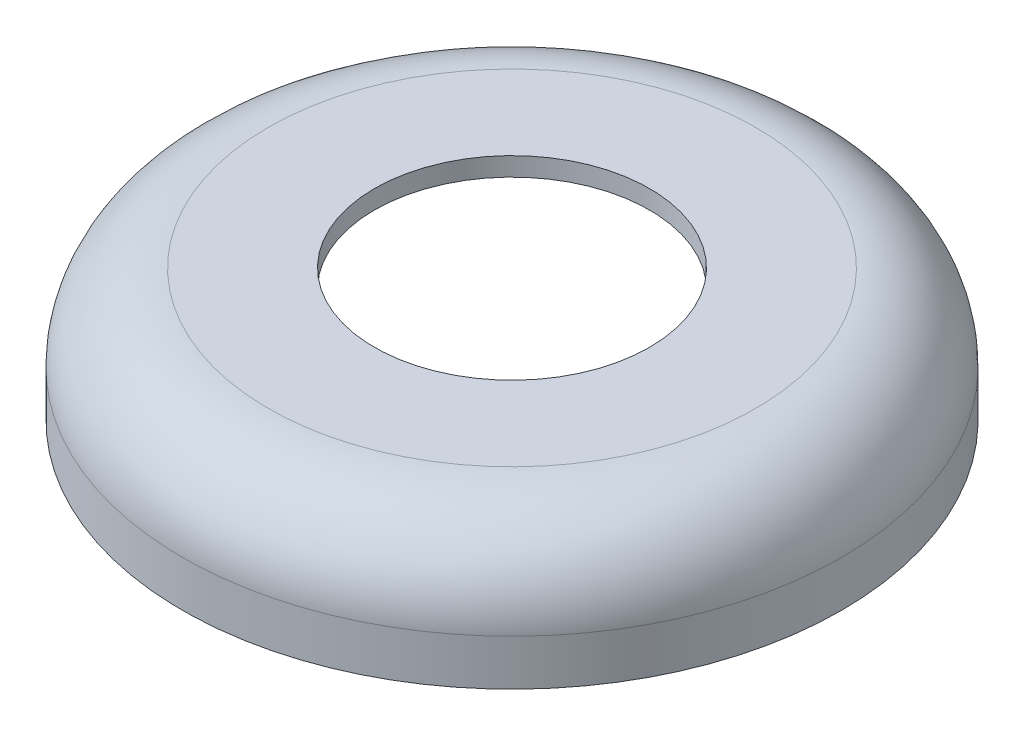
SolidWorks part; units mm, degrees
material "6061 Alloy"
ref_plane "Front Plane" through (0, 0, 0) normal (0, 0, 1) x (1, 0, 0)
ref_plane "Top Plane" through (0, 0, 0) normal (0, 1, 0) x (1, 0, 0)
ref_plane "Right Plane" through (0, 0, 0) normal (1, 0, 0) x (0, 0, -1)
sketch "Sketch1" plane through (0, 0, 0) normal (0, 0, 1) x (1, 0, 0)
  line L1 (0, 0) -> (8.5, 0)
  line L2 (0, 0) -> (0, -4.6)
  line L3 (0, -4.6) -> (11.5, -4.6)
  line L4 (11.5, -3) -> (11.5, -4.6)
  arc A0 (8.5, 0) -> (11.5, -3) centre (8.5, -3) cw
  dimension "D3" = 3
  dimension "D1" = 4.6
  dimension "D2" = 11.5
revolve "Revolve1" add sketch "Sketch1" angle 360 about L2
shell "Shell1" thickness 0.65 removed face at (-11.5, -4.6, 0)
sketch "Sketch2" plane through (0, 0, 0) normal (0, 1, 0) x (1, 0, 0)
  circle A0 centre (0, 0) radius 4.8
  dimension "D1" = 9.6
extrude "Cut-Extrude1" cut sketch "Sketch2" against normal up to body separate body
